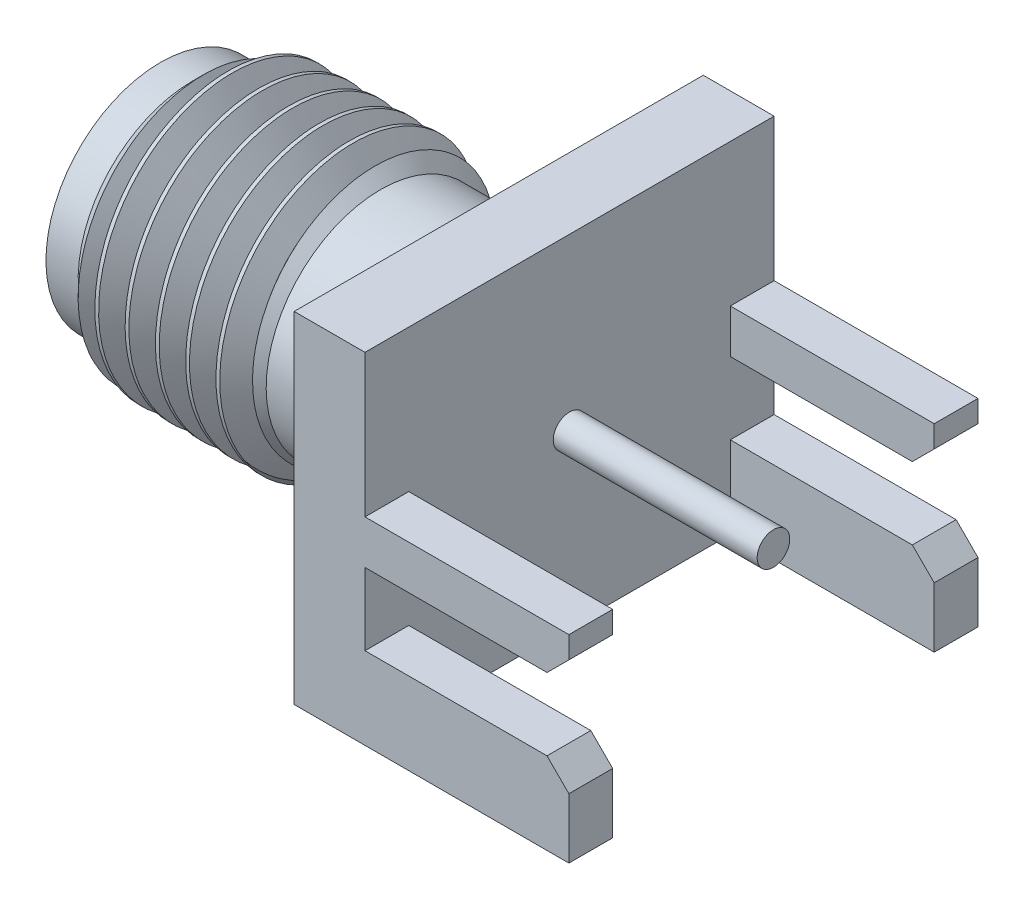
SolidWorks part; units mm, degrees
ref_plane "Front Plane" through (0, 0, 0) normal (0, 0, 1) x (1, 0, 0)
ref_plane "Top Plane" through (0, 0, 0) normal (0, 1, 0) x (1, 0, 0)
ref_plane "Right Plane" through (0, 0, 0) normal (1, 0, 0) x (0, 0, -1)
sketch "Sketch1" plane through (0, 0, 0) normal (0, 0, 1) x (1, 0, 0)
  line L0 (0, 0) -> (0, 1.68)
  line L1 (0, 1.68) -> (4.24, 1.68)
  line L2 (4.75, 2.19) -> (4.75, 2.7)
  line L3 (4.75, 2.7) -> (0, 2.7)
  line L4 (0, 2.7) -> (0, 6.02)
  line L5 (0, 6.02) -> (-1.65, 6.02)
  line L6 (-1.65, 6.02) -> (-1.65, -1.91)
  line L7 (-1.65, -1.91) -> (4.75, -1.91)
  line L8 (4.75, -1.91) -> (4.75, -0.51)
  line L9 (4.24, 0) -> (0, 0)
  line L10 (4.24, 1.68) -> (4.75, 2.19)
  line L11 (4.75, -0.51) -> (4.24, 0)
  point P4 (4.75, 1.68)
  point P11 (4.75, 0)
  dimension "D1" = 1.65
  dimension "D2" = 4.75
  dimension "D3" = 1.02
  dimension "D4" = 1.91
  dimension "D5" = 1.68
  dimension "D6" = 4.34
extrude "Boss-Extrude1" add sketch "Sketch1" along normal mid plane 9.53
sketch "Sketch2" plane through (0, 0, 0) normal (0, 1, 0) x (1, 0, 0)
  line L0 (0, -4.765) -> (0, 4.765) construction
  line L1 (0, 3.745) -> (4.75, 3.745)
  line L2 (0, 3.745) -> (0, -3.745)
  line L3 (0, -3.745) -> (4.75, -3.745)
  line L4 (4.75, 3.745) -> (4.75, -3.745)
  line L5 (4.75, -4.765) -> (4.75, 4.765) construction
  line L6 (4.75, 4.765) -> (0, 4.765) construction
  line L7 (4.75, -4.765) -> (0, -4.765) construction
  dimension "D1" = 1.02
  dimension "D2" = 1.02
extrude "Cut-Extrude1" cut sketch "Sketch2" against normal through all from surface at 2.7 starting at face at (2.375, 2.7, 0)
sketch "Sketch3" plane through (0, 0, 0) normal (0, 0, 1) x (1, 0, 0)
  line L0 (-1.65, 2.055) -> (9.0387, 2.055) construction
  line L2 (-1.65, 6.02) -> (-1.65, -1.91) construction
  line L3 (4.75, 2.055) -> (4.75, 1.675)
  line L4 (4.75, 1.675) -> (-1.65, 1.675)
  line L5 (-1.65, 1.675) -> (-1.65, -0.612)
  line L6 (-1.65, -0.612) -> (-4.4, -0.612)
  line L7 (4.75, 2.19) -> (4.75, 2.7) construction
  line L8 (-1.65, 2.055) -> (-7.6, 2.055) construction
  line L9 (-9.53, -0.612) -> (-9.53, -0.265)
  line L10 (0, 0) -> (0, 1.68) construction
  line L11 (4.75, 2.055) -> (-7.6, 2.055)
  line L12 (-8.78, -0.612) -> (-8.272, -1.12)
  line L13 (-8.272, -1.12) -> (-4.908, -1.12)
  line L14 (-4.908, -1.12) -> (-4.4, -0.612)
  line L15 (-8.78, -0.612) -> (-9.53, -0.612)
  line L16 (-9.53, -0.265) -> (-7.6, -0.265)
  line L17 (-7.6, -0.265) -> (-7.6, 2.055)
  dimension "D1" = 0.38
  dimension "D2" = 9.53
  dimension "D3" = 2.667
  dimension "D4" = 3.175
  dimension "D5" = 45
  dimension "D6" = 0.75
  dimension "D7" = 2.75
  dimension "D8" = 2.32
  dimension "D9" = 1.93
revolve "Revolve1" add sketch "Sketch3" angle 360 about L11
sketch "Sketch4" plane through (0, 0, 0) normal (0, 0, 1) x (1, 0, 0)
  line L0 (-4.4427, 5.23) -> (-4.1494, 4.722)
  line L1 (-1.65, 4.722) -> (-4.4, 4.722) construction
  line L2 (-4.1494, 4.722) -> (-4.1185, 4.722)
  line L3 (-4.1185, 4.722) -> (-3.8252, 5.23)
  line L4 (-3.8252, 5.23) -> (-4.4427, 5.23)
  line L5 (-4.1339, 5.23) -> (-4.1339, 4.722) construction
  line L6 (-3.8252, 5.23) -> (-3.7372, 5.23) construction
  line L7 (-3.7372, 5.23) -> (-3.4439, 4.722) construction
  line L8 (-4.908, 5.23) -> (-8.272, 5.23) construction
  dimension "D1" = 60
  dimension "D2" = 60
  dimension "D3" = 0.7055
  dimension "D4" = 0.088
sketch "Sketch5" plane through (-9.53, 0, 0) normal (-1, 0, 0) x (0, 0, 1)
  circle A0 centre (0, 2.055) radius 3.175
  dimension "D1" = 6.35
curve "Helix/Spiral1" pitch 0.7055 height 7.055 turns 10
sweep "Cut-Sweep1" cut profiles "Sketch4" path "Helix/Spiral1"
